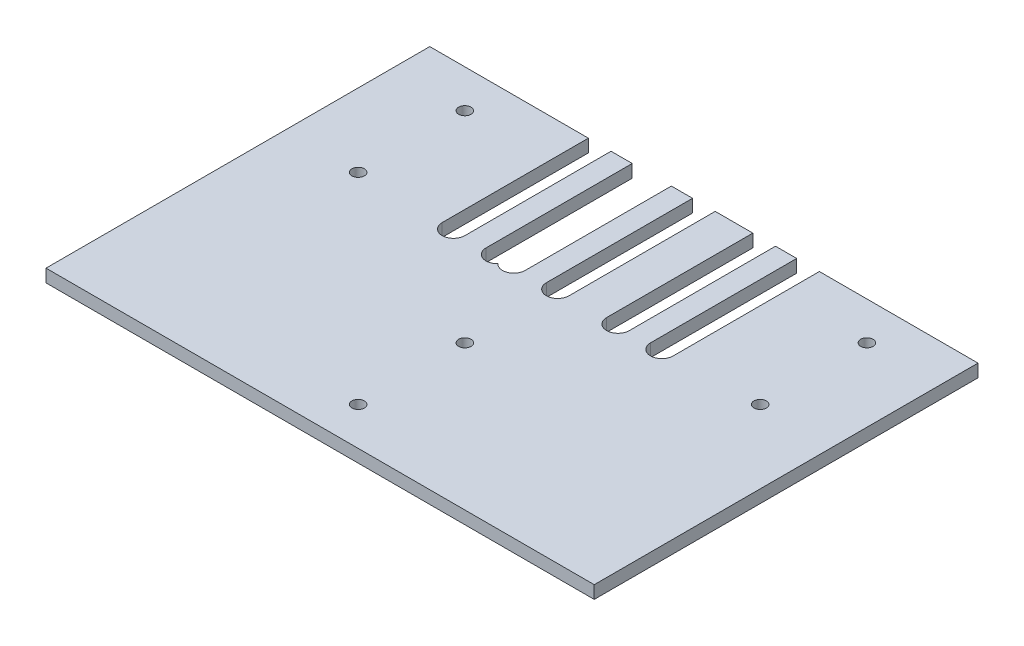
SolidWorks part; units mm, degrees
material "6061 Alloy"
ref_plane "Front Plane" through (0, 0, 0) normal (0, 0, 1) x (1, 0, 0)
ref_plane "Top Plane" through (0, 0, 0) normal (0, 1, 0) x (1, 0, 0)
ref_plane "Right Plane" through (0, 0, 0) normal (1, 0, 0) x (0, 0, -1)
sketch "Sketch1" plane through (0, 0, 0) normal (0, 1, 0) x (1, 0, 0)
  line L1 (0, 0) -> (150, 0)
  line L2 (0, 0) -> (0, 105)
  line L3 (0, 105) -> (150, 105)
  line L4 (150, 0) -> (150, 105)
  dimension "D1" = 150
  dimension "D2" = 105
extrude "Boss-Extrude1" add sketch "Sketch1" along normal blind 3.5
sketch "Sketch3" plane through (0, 3.5, 0) normal (0, 1, 0) x (1, 0, 0)
  line L0 (94.6, 105) -> (94.6, 65)
  line L2 (94.6, 105) -> (88.4, 105)
  line L3 (88.4, 105) -> (88.4, 65)
  line L4 (78.1, 105) -> (78.1, 65)
  line L5 (78.1, 105) -> (71.9, 105)
  line L6 (71.9, 105) -> (71.9, 65)
  line L7 (106.6, 105) -> (106.6, 65)
  line L8 (106.6, 105) -> (100.4, 105)
  line L9 (100.4, 105) -> (100.4, 65)
  line L10 (66.1, 105) -> (66.1, 65)
  line L11 (66.1, 105) -> (59.9, 105)
  line L12 (59.9, 105) -> (59.9, 65)
  line L16 (49.6, 105) -> (49.6, 65)
  line L17 (49.6, 105) -> (43.4, 105)
  line L18 (43.4, 105) -> (43.4, 65)
  line L19 (150, 105) -> (0, 105) construction
  line L23 (150, 0) -> (150, 105) construction
  arc A0 (88.4, 65) -> (94.6, 65) centre (91.5, 65) ccw
  arc A1 (71.9, 65) -> (78.1, 65) centre (75, 65) ccw
  arc A2 (100.4, 65) -> (106.6, 65) centre (103.5, 65) ccw
  arc A3 (59.9, 65) -> (66.1, 65) centre (63, 65) ccw
  arc A5 (43.4, 65) -> (49.6, 65) centre (46.5, 65) ccw
  dimension "D1" = 3.1
  dimension "D2" = 16.5
  dimension "D4" = 12
  dimension "D5" = 16.5
  dimension "D6" = 12
  dimension "D7" = 40
  dimension "D8" = 46.5
extrude "Cut-Extrude1" cut sketch "Sketch3" against normal through all
sketch "Sketch4" plane through (0, 3.5, 0) normal (0, 1, 0) x (1, 0, 0)
  line L0 (55.4, 105) -> (61.6, 105)
  line L1 (59.9, 105) -> (49.6, 105) construction
  line L2 (61.6, 105) -> (61.6, 65)
  line L3 (55.4, 105) -> (55.4, 65)
  line L4 (49.6, 65) -> (49.6, 105) construction
  arc A0 (55.4, 65) -> (61.6, 65) centre (58.5, 65) ccw
  arc A1 (59.9, 65) -> (66.1, 65) centre (63, 65) ccw construction
  dimension "D1" = 4.5
extrude "Cut-Extrude2" cut sketch "Sketch4" against normal through all
hole_wizard "Ø3.4 (3.4) Diameter Hole1" positions "Sketch6" profile "Sketch5" hole size "Ø3.4" standard "ANSI Metric" end condition through all
sketch "Sketch6" plane through (0, 3.5, 0) normal (0, 1, 0) x (1, 0, 0)
  line L0 (150, 0) -> (150, 105) construction
  line L2 (0, 0) -> (150, 0) construction
  line L4 (0, 105) -> (0, 0) construction
  point P0 (20, 94.6)
  point P2 (20, 65.4)
  point P4 (130, 65.4)
  point P6 (130, 94.6)
  point P8 (75, 39.6)
  point P10 (75, 10.4)
  dimension "D1" = 75
  dimension "D2" = 10.4
  dimension "D3" = 29.2
  dimension "D4" = 29.2
  dimension "D5" = 25.8
  dimension "D6" = 20
  dimension "D7" = 20
sketch "Sketch5" plane through (20, 3.5, -94.6) normal (1, 0, 0) x (0, 0, 1)
  line L0 (0, 0) -> (0, 3.5)
  line L1 (0, 3.5) -> (1.7, 3.5)
  line L2 (1.7, 3.5) -> (1.7, 0)
  line L5 (1.7, 0) -> (0, 0)
  line L11 (0, -6.35) -> (0, 107.95) construction
  dimension "Thru Hole Dia." = 3.4
  dimension "Thru Hole Depth" = 3.5
